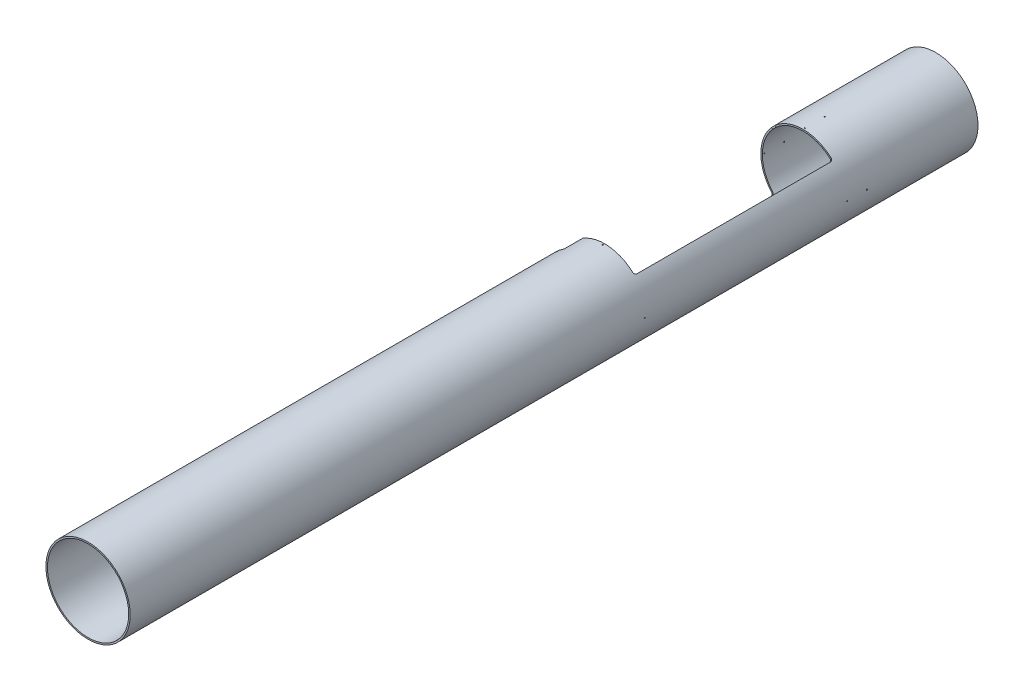
SolidWorks part; units mm, degrees
ref_plane "Front Plane" through (0, 0, 0) normal (0, 0, 1) x (1, 0, 0)
ref_plane "Top Plane" through (0, 0, 0) normal (0, 1, 0) x (1, 0, 0)
ref_plane "Right Plane" through (0, 0, 0) normal (1, 0, 0) x (0, 0, -1)
sketch "Sketch1" plane through (0, 0, 0) normal (0, 0, 1) x (1, 0, 0)
  circle A0 centre (0, 0) radius 82
  circle A1 centre (0, 0) radius 85
  dimension "D1" = 164
  dimension "D2" = 3
extrude "Boss-Extrude1" add sketch "Sketch1" along normal blind 1710
sketch "Sketch2" plane through (0, 0, 0) normal (0, 1, 0) x (1, 0, 0)
  line L0 (82, 0) -> (-82, 0) construction
  circle A0 centre (0, -224) radius 1
  circle A1 centre (0, -264) radius 1
  dimension "D1" = 2
  dimension "D3" = 2
  dimension "D2" = 224
  dimension "D4" = 40
extrude "Cut-Extrude2" cut sketch "Sketch2" against normal blind 90
pattern_circular "CirPattern1" count 4 every 90 about axis through (0, 0, 0) along (0, 0, 1) of "Cut-Extrude2"
ref_plane "Plane1" through (0, 0, 0) normal (-0.7071, 0.7071, 0) x (0.7071, 0.7071, 0)
sketch "Sketch4" plane through (0, 0, 0) normal (-0.7071, 0.7071, 0) x (0.7071, 0.7071, 0)
  line L0 (-85, 0) -> (-85, -1710) construction
  line L1 (-85, -268) -> (85, -268)
  line L2 (-85, -268) -> (-85, -668)
  line L3 (-85, -668) -> (85, -668)
  line L4 (85, -268) -> (85, -668)
  line L5 (85, -1710) -> (85, 0) construction
  line L6 (85, 0) -> (-85, 0) construction
  dimension "D1" = 268
  dimension "D2" = 400
extrude "Cut-Extrude4" cut sketch "Sketch4" along normal blind 516
sketch "Sketch5" plane through (0, 0, 268) normal (0, 0, 1) x (1, 0, 0)
  line L0 (0, 0) -> (-60.1041, 60.1041) construction
  line L1 (-64.5283, 71.3359) -> (-48.7292, 56.0617)
  line L2 (-64.5283, 71.3359) -> (-71.4789, 64.1465)
  line L3 (-48.7292, 56.0617) -> (-55.6799, 48.8722)
  line L4 (-71.4789, 64.1465) -> (-55.6799, 48.8722)
  line L5 (-64.5283, 71.3359) -> (-55.6799, 48.8722) construction
  line L6 (-48.7292, 56.0617) -> (-71.4789, 64.1465) construction
  circle A0 centre (0, 0) radius 85 construction
  dimension "D1" = 21.9753
  dimension "D2" = 10
extrude "Cut-Extrude5" cut sketch "Sketch5" against normal blind 12
fillet "Fillet2" radius 5 4 edges at (59.0434, 59.0434, 668) (-59.0434, -59.0434, 668) (-59.0434, -59.0434, 268) (59.0434, 59.0434, 268)
sketch "Sketch6" plane through (0, 0, 668) normal (0, 0, -1) x (-1, 0, 0)
  line L0 (0, 0) -> (60.1041, 60.1041) construction
  line L1 (83.9891, 55.7048) -> (64.5033, 36.2191)
  line L2 (83.9891, 55.7048) -> (55.7048, 83.9891)
  line L3 (64.5033, 36.2191) -> (36.2191, 64.5033)
  line L4 (55.7048, 83.9891) -> (36.2191, 64.5033)
  line L5 (83.9891, 55.7048) -> (36.2191, 64.5033) construction
  line L6 (64.5033, 36.2191) -> (55.7048, 83.9891) construction
  circle A0 centre (0, 0) radius 85 construction
  dimension "D1" = 40
extrude "Cut-Extrude6" cut sketch "Sketch6" against normal blind 26
sketch "Sketch8" plane through (0, 0, 0) normal (0, 1, 0) x (1, 0, 0)
  line L0 (54.3393, -668) -> (-42.0895, -668) construction
  circle A0 centre (0, -672) radius 1
  dimension "D1" = 2
  dimension "D2" = 4
extrude "Cut-Extrude7" cut sketch "Sketch8" along normal blind 246
pattern_circular "CirPattern2" count 4 every 90 about axis through (0, 0, 668) along (0, 0, -1) of "Cut-Extrude7"
sketch "Sketch9" plane through (0, 0, 694) normal (0, 0, -1) x (-1, 0, 0)
sketch "Sketch10" plane through (0, 0, 694) normal (0, 0, -1) x (-1, 0, 0)
  line L0 (40.3212, 71.4017) -> (71.4017, 40.3212)
  line L1 (0, 0) -> (60.1041, 60.1041) construction
  line L2 (0, 0) -> (85, 0) construction
  circle A0 centre (0, 0) radius 82 construction
  circle A1 centre (0, 0) radius 85 construction
  arc A2 (40.3212, 71.4017) -> (71.4017, 40.3212) centre (0, 0) cw
  dimension "D1" = 45
  dimension "D2" = 45
  dimension "D3" = 6
extrude "Boss-Extrude2" add sketch "Sketch10" against normal blind 60
fillet "Fillet3" radius 10 1 edges at (-55.8614, 55.8614, 754)
sketch "Sketch12" plane through (-55.8614, 55.8614, 0) normal (0.7071, -0.7071, 0) x (0, 0, -1)
  line L0 (-694, 0) -> (-744, 0) construction
  line L1 (-694, 21.9773) -> (-694, -21.9773) construction
  line L2 (-744, 21.9773) -> (-744, -21.9773) construction
  line L3 (-719, -23.396) -> (-719, 23.396)
  line L9 (-694, 0) -> (-706, 0)
  line L10 (-694, 0) -> (-694, 20)
  line L11 (-694, 20) -> (-706, 20)
  line L12 (-706, 0) -> (-706, 20)
  line L13 (-706, 0) -> (-694, 0)
  line L14 (-706, 0) -> (-706, -20)
  line L15 (-706, -20) -> (-694, -20)
  line L16 (-694, 0) -> (-694, -20)
  circle A0 centre (-731, 0) radius 1.25
  circle A7 centre (-713, 10.3923) radius 1.25
  circle A8 centre (-713, -10.3923) radius 1.25
  point P9 (-719, 0)
  point P17 (-738, -2.8868)
  point P18 (-728, -2.8868)
  point P25 (-721, -1.1547)
  point P26 (-719, 0)
  line M5 (-694, -21.9773) -> (-694, 21.9773)
  dimension "D1" = 2.5
  dimension "D2" = 12
  dimension "D4" = 20
  dimension "D5" = 12
  dimension "D6" = 20
  dimension "D3" = 3
extrude "Cut-Extrude8" cut sketch "Sketch12" against normal blind 101 contours L12 L9 L11 M5 | L14 L15 L9 M5 | A8 | A7 | A0 region at (-62.9325, 48.7904, 700) region at (-48.7904, 62.9325, 700)
